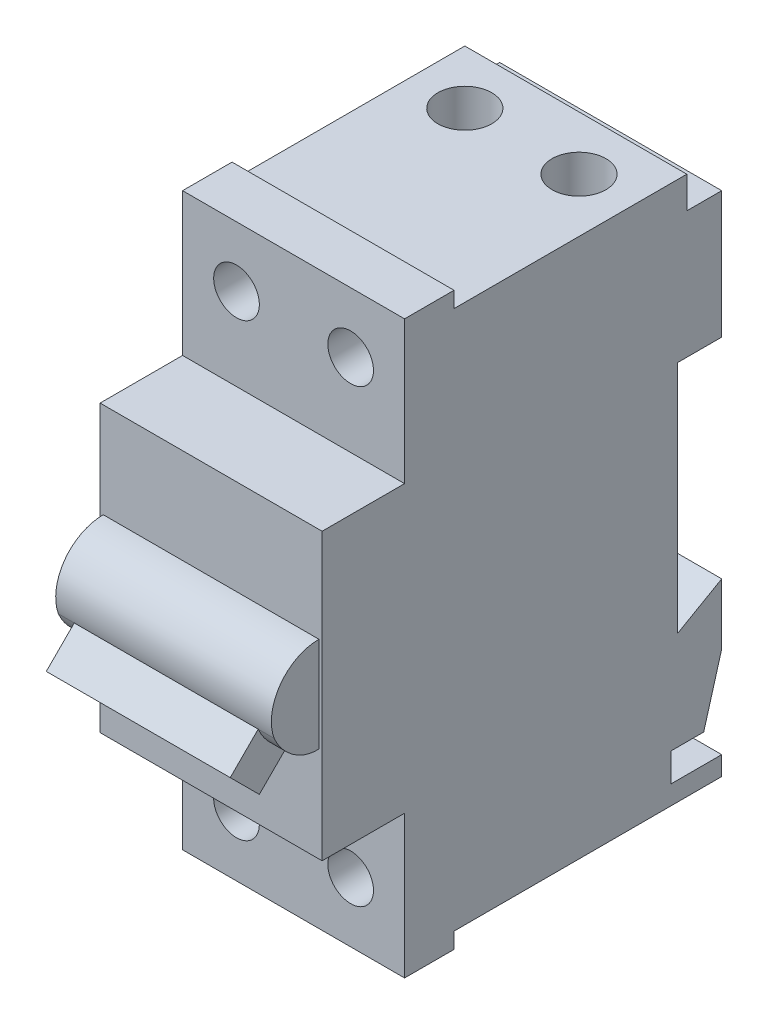
SolidWorks part; units mm, degrees
ref_plane "Спереди" through (0, 0, 0) normal (0, 0, 1) x (1, 0, 0)
ref_plane "Сверху" through (0, 0, 0) normal (0, 1, 0) x (1, 0, 0)
ref_plane "Справа" through (0, 0, 0) normal (1, 0, 0) x (0, 0, -1)
sketch "Эскиз1" plane through (0, 0, 0) normal (0, 0, 1) x (1, 0, 0)
  line L0 (0, 75.6302) -> (0, -72.8446) construction
  line L1 (-73.4017, 0) -> (52.7879, 0) construction
  line L3 (-17.5, -22.5) -> (17.5, -22.5)
  line L4 (-17.5, -22.5) -> (-17.5, 22.5)
  line L5 (-17.5, 22.5) -> (17.5, 22.5)
  line L6 (17.5, -22.5) -> (17.5, 22.5)
  dimension "D1" = 35
  dimension "D2" = 45
extrude "Вытянуть1" add sketch "Эскиз1" along normal blind 13
sketch "Эскиз2" plane through (0, 0, 0) normal (0, 0, -1) x (-1, 0, 0)
  line L0 (31.1022, 0) -> (-31.6373, 0) construction
  line L1 (17.5, -45) -> (-17.5, -45)
  line L2 (17.5, -45) -> (17.5, 45)
  line L3 (17.5, 45) -> (-17.5, 45)
  line L4 (-17.5, -45) -> (-17.5, 45)
  line L5 (-17.5, -22.5) -> (-17.5, 22.5) construction
  line L9 (17.5, 22.5) -> (17.5, -22.5) construction
  line L10 (0, 50.7668) -> (0, -50.9006) construction
  circle A0 centre (9, 35.5) radius 3.6
  circle A1 centre (-9, 35.5) radius 3.6
  circle A2 centre (-9, -35.5) radius 3.6
  circle A3 centre (9, -35.5) radius 3.6
  dimension "D2" = 18
  dimension "D3" = 7.2
  dimension "D4" = 9.5
  dimension "D1" = 90
extrude "Вытянуть2" add sketch "Эскиз2" along normal blind 7.8
sketch "Эскиз3" plane through (0, 0, -7.8) normal (0, 0, -1) x (-1, 0, 0)
  line L0 (-17.5, 42.5) -> (17.5, 42.5)
  line L1 (-28.708, 0) -> (21.9987, 0) construction
  line L2 (-17.5, -42.5) -> (17.5, -42.5)
  line L3 (17.5, 45) -> (-17.5, 45) construction
  line L4 (17.5, -45) -> (17.5, 45)
  line L5 (17.5, 45) -> (-17.5, 45)
  line L6 (-17.5, 45) -> (-17.5, -45)
  line L7 (-17.5, -45) -> (17.5, -45)
  line L8 (17.5, -42.5) -> (17.5, 42.5)
  line L10 (-17.5, 42.5) -> (-17.5, -42.5)
  dimension "D2" = 2.5
  dimension "D1" = 0
extrude "Вытянуть3" add sketch "Эскиз3" along normal offset from surface (42.2 mm away) 50
sketch "Эскиз4" plane through (17.5, 0, 0) normal (1, 0, 0) x (0, 0, -1)
  line L0 (-20.2382, 0) -> (72.3125, 0) construction
  line L1 (72.3125, -50.9347) -> (72.3125, 49.7413)
  line L2 (72.3125, 49.7413) -> (44.5, 49.7413)
  line L3 (44.5, 49.7413) -> (44.5, 37.5)
  line L4 (44.5, 37.5) -> (50, 37.5)
  line L5 (50, 42.5) -> (50, -42.5) construction
  line L6 (50, 42.5) -> (7.8, 42.5) construction
  line L7 (50, 37.5) -> (50, 17.5)
  line L8 (50, 17.5) -> (43, 17.5)
  line L9 (43, 17.5) -> (43, -19.5)
  line L10 (0, -22.5) -> (0, -45) construction
  line L12 (50, -15.5) -> (50, -25.0675)
  line L13 (50, -25.0675) -> (47.1596, -35)
  line L14 (47.1596, -35) -> (42, -35)
  line L15 (42, -35) -> (42, -39.5)
  line L16 (42, -39.5) -> (50, -39.5)
  line L17 (50, -39.5) -> (50, -42.5)
  line L18 (50, -42.5) -> (7.8, -42.5) construction
  line L19 (50, -42.5) -> (72.3125, -50.9347)
  line L20 (43, -19.5) -> (50, -15.5)
  dimension "D1" = 5
  dimension "D2" = 5.5
  dimension "D3" = 25
  dimension "D4" = 7
  dimension "D5" = 33
  dimension "D6" = 37
  dimension "D7" = 3
  dimension "D8" = 4.5
  dimension "D9" = 42
extrude "Вырез-Вытянуть1" cut sketch "Эскиз4" against normal blind 65
sketch "Эскиз5" plane through (0, 0, 0) normal (1, 0, 0) x (0, 0, -1)
  line L0 (0, 0) -> (-26, 0) construction
  line L1 (-13, -22.5) -> (-13, 22.5) construction
  line L2 (-15.4873, -7.0755) -> (-19.8983, -11.4865)
  line L3 (-19.8983, -11.4865) -> (-24.4865, -6.8983)
  line L4 (-24.4865, -6.8983) -> (-20.0755, -2.4873)
  line L5 (-13, 0) -> (-30.938, -17.938) construction
  arc A0 (-15.4873, -7.0755) -> (-20.0755, -2.4873) centre (-13, 0) ccw
  dimension "D1" = 15
  dimension "D3" = 13
  dimension "D2" = 6.4887
  dimension "D4" = 45
extrude "Вытянуть4" add sketch "Эскиз5" along normal blind 17 and the other way blind 17
sketch "Эскиз6" plane through (17, 0, 0) normal (1, 0, 0) x (0, 0, -1)
  line L4 (-13, -7.5) -> (-13, 7.5)
  line L5 (-20.0755, -2.4873) -> (-24.4865, -6.8983)
  line L6 (-24.4865, -6.8983) -> (-19.8983, -11.4865)
  line L7 (-19.8983, -11.4865) -> (-15.4873, -7.0755)
  line L9 (-20.0755, -2.4873) -> (-24.4865, -6.8983)
  line L10 (-24.4865, -6.8983) -> (-19.8983, -11.4865)
  line L11 (-19.8983, -11.4865) -> (-15.4873, -7.0755)
  arc A0 (-15.4873, -7.0755) -> (-20.0755, -2.4873) centre (-11.9651, 1.0349) cw
  arc A2 (-13, 7.5) -> (-20.0755, -2.4873) centre (-13, 0) ccw
  arc A3 (-15.4873, -7.0755) -> (-13, -7.5) centre (-13, 0) ccw
  dimension "D1" = 0
extrude "Вырез-Вытянуть2" cut sketch "Эскиз6" against normal blind 2.5
sketch "Эскиз7" plane through (-17, 0, 0) normal (-1, 0, 0) x (0, 0, 1)
  line L0 (20.0755, -2.4873) -> (24.4865, -6.8983) construction
  line L1 (20.0755, -2.4873) -> (24.4865, -6.8983)
  line L2 (24.4865, -6.8983) -> (19.8983, -11.4865) construction
  line L3 (24.4865, -6.8983) -> (19.8983, -11.4865)
  line L4 (19.8983, -11.4865) -> (15.4873, -7.0755) construction
  line L5 (19.8983, -11.4865) -> (15.4873, -7.0755)
  arc A0 (15.4873, -7.0755) -> (20.0755, -2.4873) centre (11.9651, 1.0349) ccw construction
  arc A1 (15.4873, -7.0755) -> (20.0755, -2.4873) centre (11.9651, 1.0349) ccw
extrude "Вырез-Вытянуть3" cut sketch "Эскиз7" against normal blind 2.5
sketch "Эскиз8" plane through (0, -42.5, 0) normal (0, -1, 0) x (1, 0, 0)
  line L0 (0, 24.0255) -> (0, -66.3819) construction
  line L1 (17.5, -50) -> (17.5, -7.8) construction
  line L2 (-17.5, -50) -> (-17.5, -7.8) construction
  line L3 (17.5, 0) -> (-17.5, 0) construction
  circle A0 centre (9, -36) radius 4.25
  circle A1 centre (-9, -36) radius 4.25
  dimension "D2" = 18
  dimension "D3" = 8.5
  dimension "D1" = 36
extrude "Вырез-Вытянуть4" cut sketch "Эскиз8" against normal blind 10
sketch "Эскиз9" plane through (0, 42.5, 0) normal (0, 1, 0) x (-1, 0, 0)
  circle A0 centre (-9, -36) radius 4.25 construction
  circle A1 centre (-9, -36) radius 4.25
  circle A2 centre (9, -36) radius 4.25 construction
  circle A3 centre (9, -36) radius 4.25
extrude "Вырез-Вытянуть5" cut sketch "Эскиз9" against normal blind 10
